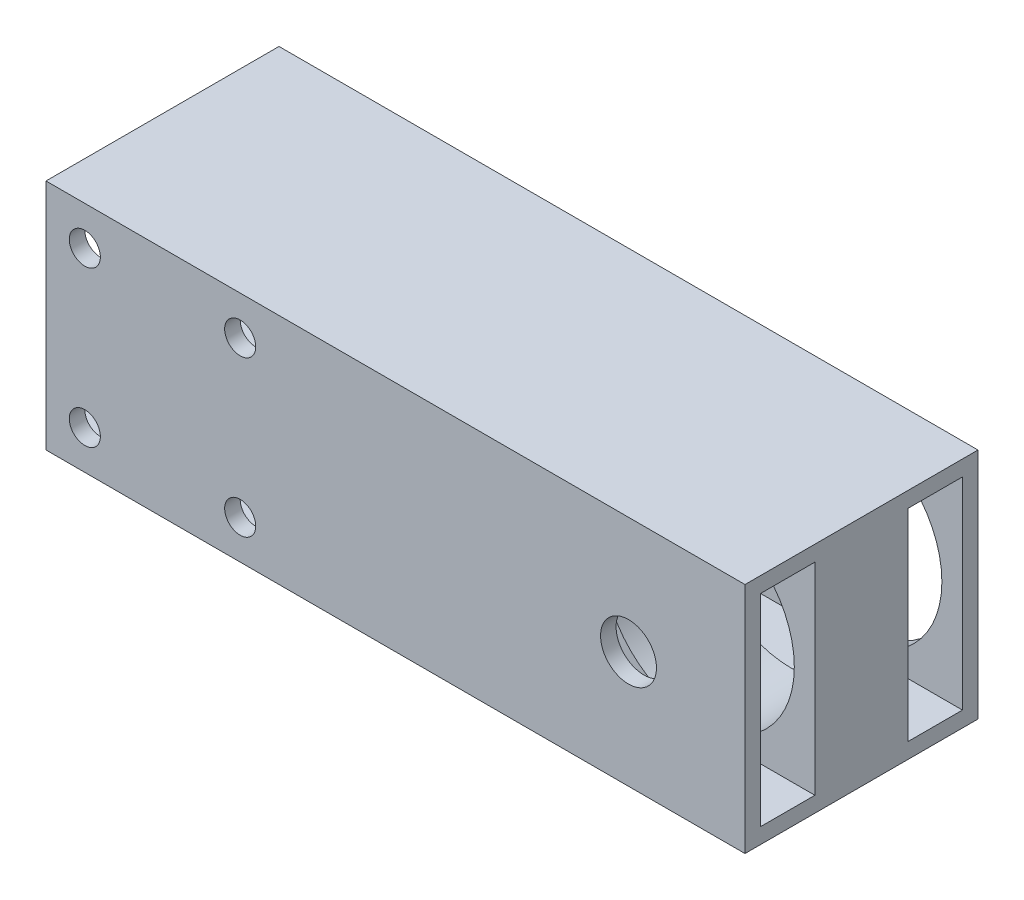
SolidWorks part; units mm, degrees
ref_plane "Front Plane" through (0, 0, 0) normal (0, 0, 1) x (1, 0, 0)
ref_plane "Top Plane" through (0, 0, 0) normal (0, 1, 0) x (1, 0, 0)
ref_plane "Right Plane" through (0, 0, 0) normal (1, 0, 0) x (0, 0, -1)
sketch "Sketch1" plane through (0, 0, 0) normal (1, 0, 0) x (0, 0, -1)
  line L1 (-15, -15) -> (15, -15)
  line L2 (-15, -15) -> (-15, 15)
  line L3 (-15, 15) -> (15, 15)
  line L4 (15, -15) -> (15, 15)
  line L5 (-15, -15) -> (15, 15) construction
  line L6 (-15, 15) -> (15, -15) construction
  line L11 (-5.1844, 5.1844) -> (5.1844, -5.1844) construction
  line L12 (-5.1844, -5.1844) -> (5.1844, 5.1844) construction
  line L13 (-13, 13) -> (-6, 13)
  line L14 (-13, 13) -> (-13, -13)
  line L15 (-13, -13) -> (-6, -13)
  line L16 (-6, 13) -> (-6, -13)
  line L17 (13, 13) -> (6, 13)
  line L18 (13, 13) -> (13, -13)
  line L19 (13, -13) -> (6, -13)
  line L20 (6, 13) -> (6, -13)
  point P0 (0, 0)
  point P7 (0, 0)
  dimension "D1" = 30
  dimension "D2" = 30
  dimension "D3" = 2
  dimension "D4" = 7
  dimension "D5" = 2
  dimension "D6" = 7
  dimension "D7" = 2
  dimension "D8" = 2
extrude "Boss-Extrude3" add sketch "Sketch1" along normal blind 90
sketch "Sketch6" plane through (0, 0, -15) normal (0, 0, -1) x (-1, 0, 0)
  line L0 (-90, -15) -> (-90, 15) construction
  circle A0 centre (-75, 0) radius 12.35
  dimension "D2" = 24.7
  dimension "D1" = 15
extrude "Cut-Extrude5" cut sketch "Sketch6" against normal blind 23
sketch "Sketch8" plane through (0, 0, 15) normal (0, 0, 1) x (1, 0, 0)
  line L0 (90, 15) -> (90, -15) construction
  circle A0 centre (75, 0) radius 3.6
  dimension "D2" = 7.2
  dimension "D1" = 15
extrude "Cut-Extrude6" cut sketch "Sketch8" against normal blind 17
sketch "Sketch9" plane through (0, 0, 0) normal (-1, 0, 0) x (0, 0, 1)
  line L0 (-6, 13) -> (6, 13)
  line L1 (-6, -13) -> (6, -13)
  line L2 (-6, 13) -> (-6, -13)
  line L3 (6, 13) -> (6, -13)
extrude "Cut-Extrude7" cut sketch "Sketch9" against normal blind 59
sketch "Sketch10" plane through (0, 0, -15) normal (0, 0, -1) x (-1, 0, 0)
  line L0 (0, 15) -> (-30.0029, 15)
  line L1 (-90, 15) -> (0, 15) construction
  line L2 (-30.0029, 15) -> (-30.0029, -15)
  line L3 (-90, -15) -> (0, -15) construction
  line L4 (-30.0029, -15) -> (0, -15)
  line L5 (-25.0029, 10) -> (0, 10)
  line L6 (0, -15) -> (0, 15) construction
  line L7 (-25.0029, 10) -> (-25.0029, -15)
  circle A0 centre (-25.0029, 10) radius 2
  circle A1 centre (-5, 10) radius 2
  circle A2 centre (-25.0029, -10) radius 2
  circle A3 centre (-5, -10) radius 2
  dimension "D3" = 4
  dimension "D4" = 5
  dimension "D5" = 4
  dimension "D7" = 4
  dimension "D8" = 4
  dimension "D1" = 5
  dimension "D2" = 5
  dimension "D6" = 5
extrude "Cut-Extrude8" cut sketch "Sketch10" against normal blind 34 contours A0 | A1 | A3 | A2
